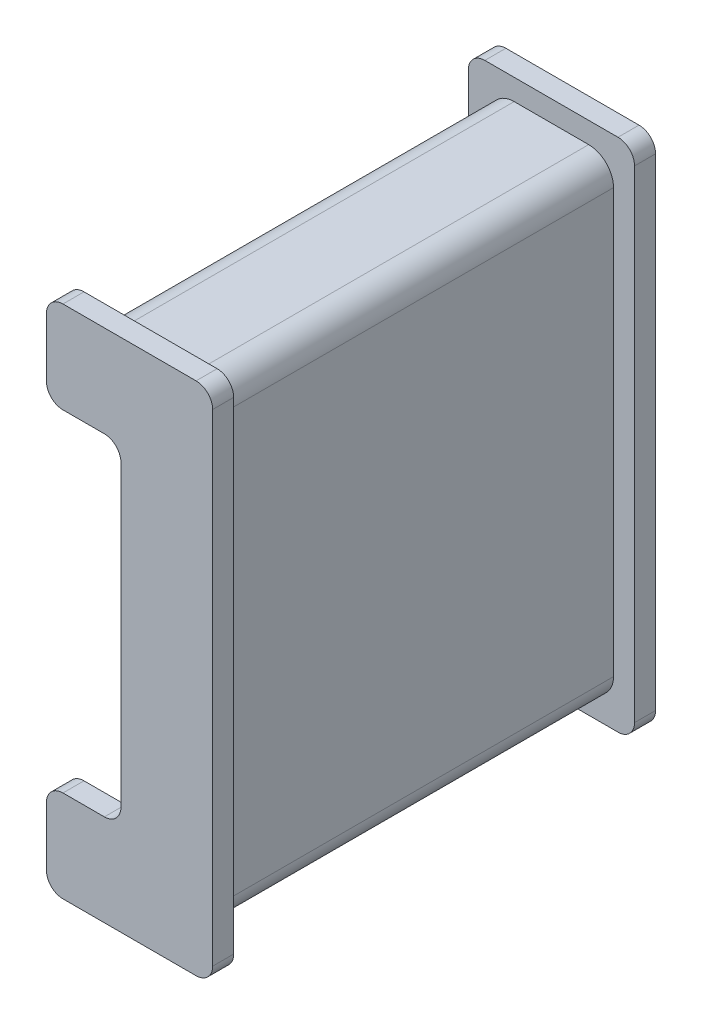
SolidWorks part; units mm, degrees
material "ABS"
ref_plane "X-Y Datum" through (0, 0, 0) normal (0, 0, 1) x (1, 0, 0)
ref_plane "X-Z Datum" through (0, 0, 0) normal (0, 1, 0) x (1, 0, 0)
ref_plane "Y-Z Datum" through (0, 0, 0) normal (1, 0, 0) x (0, 0, -1)
sketch "Sketch1" plane through (0, 0, 0) normal (0, 0, 1) x (1, 0, 0)
  line L1 (0, 0) -> (15, 0)
  line L2 (0, 0) -> (0, 6)
  line L3 (0, 6) -> (9, 6)
  line L4 (15, 0) -> (15, 6.15)
  line L6 (15, 6.15) -> (15, 57.15)
  line L8 (9, 6) -> (9, 51.15)
  line L9 (15, 57.15) -> (0, 57.15)
  line L10 (15, 57.15) -> (15, 53.7541)
  line L11 (9, 51.15) -> (0, 51.15)
  line L12 (0, 57.15) -> (0, 51.15)
  point P12 (0, 54.15)
  dimension "D1" = 15
  dimension "D2" = 57.15
  dimension "D3" = 6
  dimension "D4" = 6
  dimension "D5" = 6
  dimension "D6" = 15
extrude "Boss-Extrude1" add sketch "Sketch1" along normal blind 48.42 contours L9 L12 L11 L8 L3 L2 L1 L4 L6 region at (10.2036, 28.575, 0)
sketch "Sketch2" plane through (0, 0, 48.42) normal (0, 0, 1) x (1, 0, 0)
  line L17 (-2.54, 48.61) -> (6.46, 48.61)
  line L18 (-2.54, 59.69) -> (17.54, 59.69)
  line L19 (17.54, 59.69) -> (17.54, -2.54)
  line L20 (17.54, -2.54) -> (-2.54, -2.54)
  line L21 (-2.54, 8.54) -> (6.46, 8.54)
  line L22 (6.46, 48.61) -> (6.46, 8.54)
  line L23 (9, 6) -> (9, 51.15) construction
  line L24 (15, 0) -> (15, 57.15) construction
  line L25 (15, 57.15) -> (0, 57.15) construction
  line L26 (9, 51.15) -> (0, 51.15) construction
  line L27 (0, 6) -> (9, 6) construction
  line L28 (0, 0) -> (15, 0) construction
  line L29 (-2.54, 59.69) -> (-2.54, 48.61)
  line L30 (-2.54, 8.54) -> (-2.54, -2.54)
  dimension "D2" = 2.54
  dimension "D3" = 2.54
  dimension "D4" = 2.54
  dimension "D5" = 2.54
  dimension "D6" = 2.54
  dimension "D8" = 2.54
extrude "Boss-Extrude2" add sketch "Sketch2" along normal blind 2.54
sketch "Sketch3" plane through (0, 0, 0) normal (0, 0, -1) x (-1, 0, 0)
  line L24 (-17.54, -2.54) -> (-17.54, 59.69) construction
  line L29 (2.54, 59.69) -> (-17.54, 59.69)
  line L30 (2.54, 59.69) -> (2.54, 48.1569)
  line L31 (2.54, 48.1569) -> (-6.46, 48.1569)
  line L32 (-17.54, 59.69) -> (-17.54, 48.1569)
  line L33 (2.54, -2.54) -> (-17.54, -2.54) construction
  line L35 (-17.54, 48.1569) -> (-17.54, -2.54)
  line L36 (-17.54, -2.54) -> (-6.46, -2.54)
  line L37 (-6.46, 48.1569) -> (-6.46, 8.54)
  line L39 (-6.46, -2.54) -> (2.54, -2.54)
  line L41 (-6.46, 8.54) -> (2.54, 8.54)
  line L42 (2.54, -2.54) -> (2.54, 8.54)
extrude "Boss-Extrude3" add sketch "Sketch3" along normal blind 2.54
fillet "Fillet4" radius 3 8 edges at (0, 6, 24.21) (9, 6, 24.21) (15, 0, 24.21) (0, 0, 24.21) (15, 57.15, 24.21) (0, 57.15, 24.21) (9, 51.15, 24.21) (0, 51.15, 24.21)
fillet "Fillet5" radius 2 16 edges at (-2.54, 59.69, -1.27) (17.54, 59.69, -1.27) (17.54, -2.54, -1.27) (-2.54, -2.54, -1.27) (-2.54, 8.54, -1.27) (6.46, 8.54, -1.27) (-2.54, 48.1569, -1.27) (6.46, 48.1569, -1.27) (-2.54, 8.54, 49.69) (6.46, 8.54, 49.69) (17.54, -2.54, 49.69) (-2.54, -2.54, 49.69) (17.54, 59.69, 49.69) (-2.54, 59.69, 49.69) (6.46, 48.61, 49.69) (-2.54, 48.61, 49.69)
